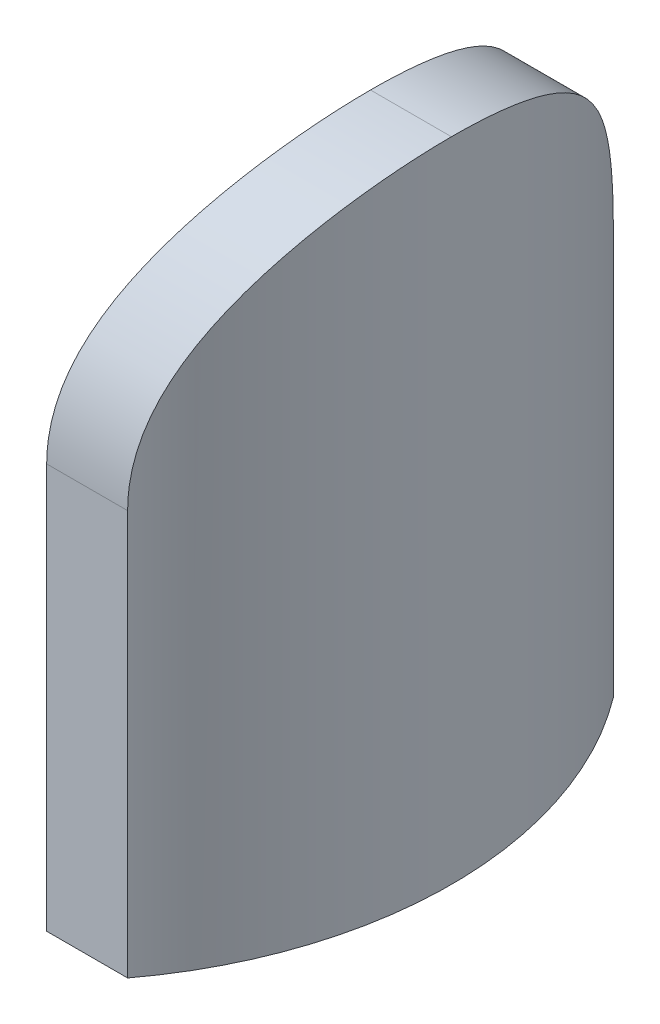
SolidWorks part; units mm, degrees
ref_plane "Front Plane" through (0, 0, 0) normal (0, 0, 1) x (1, 0, 0)
ref_plane "Top Plane" through (0, 0, 0) normal (0, 1, 0) x (1, 0, 0)
ref_plane "Right Plane" through (0, 0, 0) normal (1, 0, 0) x (0, 0, -1)
sketch "Sketch1" plane through (0, 0, 0) normal (0, 1, 0) x (1, 0, 0)
  line L1 (0, 0) -> (10, 0)
  line L2 (0, 0) -> (0, 30)
  line L3 (0, 30) -> (10, 30)
  line L4 (10, 0) -> (10, 30)
  dimension "D1" = 30
  dimension "D2" = 10
extrude "Boss-Extrude1" add sketch "Sketch1" along normal blind 40
fillet "Fillet1" radius 15 2 edges at (5, 40, -30) (5, 40, 0)
sketch "Sketch2" plane through (0, 0, 0) normal (0, -1, 0) x (1, 0, 0)
  line L0 (0, 0) -> (5, 0)
  line L1 (0, 0) -> (10, 0) construction
  line L2 (0, -30) -> (5, -30)
  line L3 (10, -30) -> (0, -30) construction
  line L4 (5, 0) -> (5, -30) construction
  line L5 (0, 0) -> (-5.4074, 0)
  line L6 (-5.4074, 0) -> (-5.4074, -30)
  line L7 (-5.4074, -30) -> (0, -30)
  line L8 (5, 0) -> (16.8415, 0)
  line L9 (16.8415, 0) -> (16.8415, -30)
  line L10 (16.8415, -30) -> (5, -30)
  arc A0 (5, 0) -> (5, -30) centre (-15, -15) cw
  arc A1 (0, 0) -> (0, -30) centre (-20, -15) cw
  line M1 (0, 0) -> (0, -30)
  line M2 (0, -30) -> (10, -30)
  line M3 (10, -30) -> (10, 0)
  line M4 (10, 0) -> (0, 0)
extrude "Cut-Extrude1" cut sketch "Sketch2" against normal blind 40 contours A0 M4 M3 | A0 M3 M2 | A1 M1 region at (2.0182, 0, -15) region at (8.5298, 0, -3.6709) region at (8.5298, 0, -26.3291)
shell "Shell2" thickness 1 removed face at (5, 0, -15)
